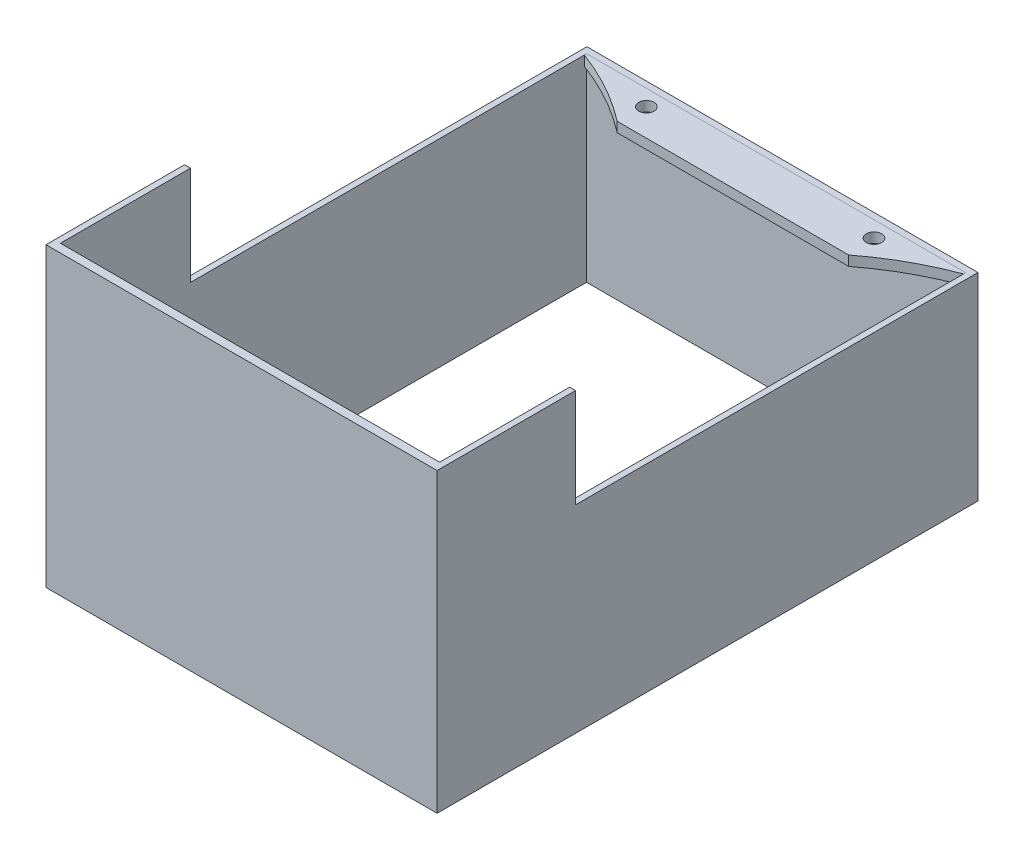
SolidWorks part; units mm, degrees
note: The reader was unsure of these and kept them because the rebuilt part matched: shared geometry of "Sketch1<5>".
ref_plane "Front Plane" through (0, 0, 0) normal (0, 0, 1) x (1, 0, 0)
ref_plane "Top Plane" through (0, 0, 0) normal (0, 1, 0) x (1, 0, 0)
ref_plane "Right Plane" through (0, 0, 0) normal (1, 0, 0) x (0, 0, -1)
sketch "Sketch1" plane through (0, 0, 0) normal (0, 1, 0) x (1, 0, 0)
  line L0 (0, 8.5) -> (0, -8.5) construction
  line L1 (-27.5, -1.5) -> (-27.5, 8.5)
  line L2 (-27.5, 8.5) -> (27.5, 8.5)
  line L3 (-27.5, -1.5) -> (27.5, -1.5)
  line L4 (27.5, -1.5) -> (27.5, 8.5)
  line L5 (0, 0) -> (0, -46.8) construction
  line L6 (0, -46.8) -> (-58.32, -46.8) construction
  line L7 (-38.32, 5.5068) -> (-38.32, -99.1068)
  line L8 (-39.52, -100.8222) -> (-39.52, 7.2222)
  line L9 (39.52, -100.8222) -> (39.52, 7.2222)
  line L10 (38.32, 5.5068) -> (38.32, -99.1068)
  line L11 (-27.5, 8.5) -> (-39.52, 8.5)
  line L12 (-39.52, 8.5) -> (-39.52, 7.2222)
  line L13 (27.5, 8.5) -> (39.52, 8.5)
  line L14 (39.52, 8.5) -> (39.52, 7.2222)
  line L15 (-39.52, 7.2222) -> (39.52, 7.2222)
  line L16 (-39.52, -100.8222) -> (39.52, -100.8222)
  line L17 (-38.32, -99.1068) -> (38.32, -99.1068)
  line L18 (-38.32, 5.5068) -> (-38.32, 8.5)
  line L19 (38.32, 5.5068) -> (38.32, 8.5)
  line L20 (38.32, 5.5068) -> (39.52, 5.5068)
  line L21 (38.32, 5.5068) -> (38.32, 6.7896)
  circle A0 centre (-23, 4) radius 1.55
  circle A1 centre (23, 4) radius 1.55
  arc A2 (-38.32, -99.1068) -> (-38.32, 5.5068) centre (-58.32, -46.8) ccw
  arc A3 (-39.52, -100.8222) -> (-39.52, 7.2222) centre (-58.32, -46.8) ccw
  arc A4 (39.52, -100.8222) -> (39.52, 7.2222) centre (58.32, -46.8) cw
  arc A5 (38.32, -99.1068) -> (38.32, 5.5068) centre (58.32, -46.8) cw
  point P3 (0, 8.5)
  point P4 (0, 0)
  dimension "D1" = 3.1
  dimension "D4" = 4.5
  dimension "D7" = 112
  dimension "D10" = 1.2
  dimension "D2" = 23
  dimension "D3" = 4
  dimension "D5" = 10
  dimension "D6" = 4.5
  dimension "D8" = 46.8
  dimension "D9" = 58.32
  dimension "D11" = 20
  dimension "D12" = 1.2
extrude "Boss-Extrude1" add sketch "Sketch1" along normal blind 2 contours L3 A4 L4 L2 L1 A3 A0 A1 | L4 A4 L14 L13 | A3 L1 L11 L12
extrude "Boss-Extrude2" add sketch "Sketch1<5>" against normal blind 10 from surface at 2 separate body contours L16 A4 L17 A3 | L8 A3 L17 L7 L18 | A4 L9 L20 L10 L17 | L18 L15 L1 L11 | L1 L15 L4 L2 | L15 L18 L11 L12 | L15 L19 L13 L4 | L19 L15 L14 L13 | A4 L19 L20 L9 | L19 A4 L15 | A3 L18 L15
sketch "Sketch1<5>" plane through (0, 0, 0) normal (0, 1, 0) x (1, 0, 0) same geometry as "Sketch1"
sketch "Sketch3" plane through (0, -8, 0) normal (0, -1, 0) x (1, 0, 0)
  line L0 (-38.32, -7.2222) -> (38.32, -7.2222) construction
  line L1 (38.32, -7.2222) -> (38.32, 99.1068) construction
  line L2 (38.32, 99.1068) -> (-38.32, 99.1068) construction
  line L3 (-38.32, -7.2222) -> (-38.32, 99.1068) construction
  line L4 (-39.52, -8.5) -> (39.52, -8.5)
  line L5 (39.52, -8.5) -> (39.52, 100.8222)
  line L6 (39.52, 100.8222) -> (-39.52, 100.8222)
  line L7 (-39.52, 100.8222) -> (-39.52, -8.5)
  line L8 (-39.52, -8.5) -> (39.52, -8.5)
  line L9 (39.52, -8.5) -> (39.52, 100.8222)
  line L10 (39.52, 100.8222) -> (-39.52, 100.8222)
  line L11 (-39.52, 100.8222) -> (-39.52, -8.5)
  line L12 (-38.32, -7.2222) -> (38.32, -7.2222)
  line L13 (38.32, -7.2222) -> (38.32, 99.1068)
  line L14 (38.32, 99.1068) -> (-38.32, 99.1068)
  line L15 (-38.32, -7.2222) -> (-38.32, 99.1068)
  line L16 (-39.52, 72.8222) -> (-38.32, 72.8222)
  line L17 (0, 0) -> (0, 99.1068) construction
  line L18 (39.52, 72.8222) -> (38.32, 72.8222)
  line M11 (38.32, 99.1068) -> (38.32, -7.2222)
  line M14 (-38.32, 99.1068) -> (38.32, 99.1068)
  line M17 (39.52, 100.8222) -> (-39.52, 100.8222)
  line M18 (-39.52, 100.8222) -> (-39.52, -8.5)
  dimension "D2" = 28
  dimension "D1" = 0
extrude "Boss-Extrude3" add sketch "Sketch3" against normal blind 20 from surface contours L18 L9 L16 L15 L14 M17 M18 M14 M11
sketch "Sketch4" plane through (0, -8, 0) normal (0, -1, 0) x (1, 0, 0)
  line L0 (-38.32, -7.2222) -> (38.32, -7.2222) construction
  line L1 (38.32, -7.2222) -> (38.32, 99.1068) construction
  line L2 (38.32, 99.1068) -> (-38.32, 99.1068) construction
  line L3 (-38.32, -7.2222) -> (-38.32, 99.1068) construction
  line L4 (-39.52, -8.5) -> (39.52, -8.5)
  line L5 (39.52, -8.5) -> (39.52, 100.8222)
  line L6 (39.52, 100.8222) -> (-39.52, 100.8222)
  line L7 (-39.52, 100.8222) -> (-39.52, -8.5)
  line L8 (-39.52, -8.5) -> (39.52, -8.5)
  line L9 (39.52, -8.5) -> (39.52, 100.8222)
  line L10 (39.52, 100.8222) -> (-39.52, 100.8222)
  line L11 (-39.52, 100.8222) -> (-39.52, -8.5)
  line L12 (-38.32, -7.2222) -> (38.32, -7.2222)
  line L13 (38.32, -7.2222) -> (38.32, 99.1068)
  line L14 (38.32, 99.1068) -> (-38.32, 99.1068)
  line L15 (-38.32, -7.2222) -> (-38.32, 99.1068)
  line M9 (38.32, 99.1068) -> (38.32, -7.2222)
  line M10 (38.32, -7.2222) -> (-38.32, -7.2222)
  line M11 (-38.32, -7.2222) -> (-38.32, 99.1068)
  line M12 (-38.32, 99.1068) -> (38.32, 99.1068)
  line M13 (-39.52, -8.5) -> (39.52, -8.5)
  line M14 (39.52, -8.5) -> (39.52, 100.8222)
  line M15 (39.52, 100.8222) -> (-39.52, 100.8222)
  line M16 (-39.52, 100.8222) -> (-39.52, -8.5)
  dimension "D1" = 0
extrude "Boss-Extrude4" add sketch "Sketch4" along normal blind 30 contours M16 M13 M14 M15 M12 M9 M10 M11
